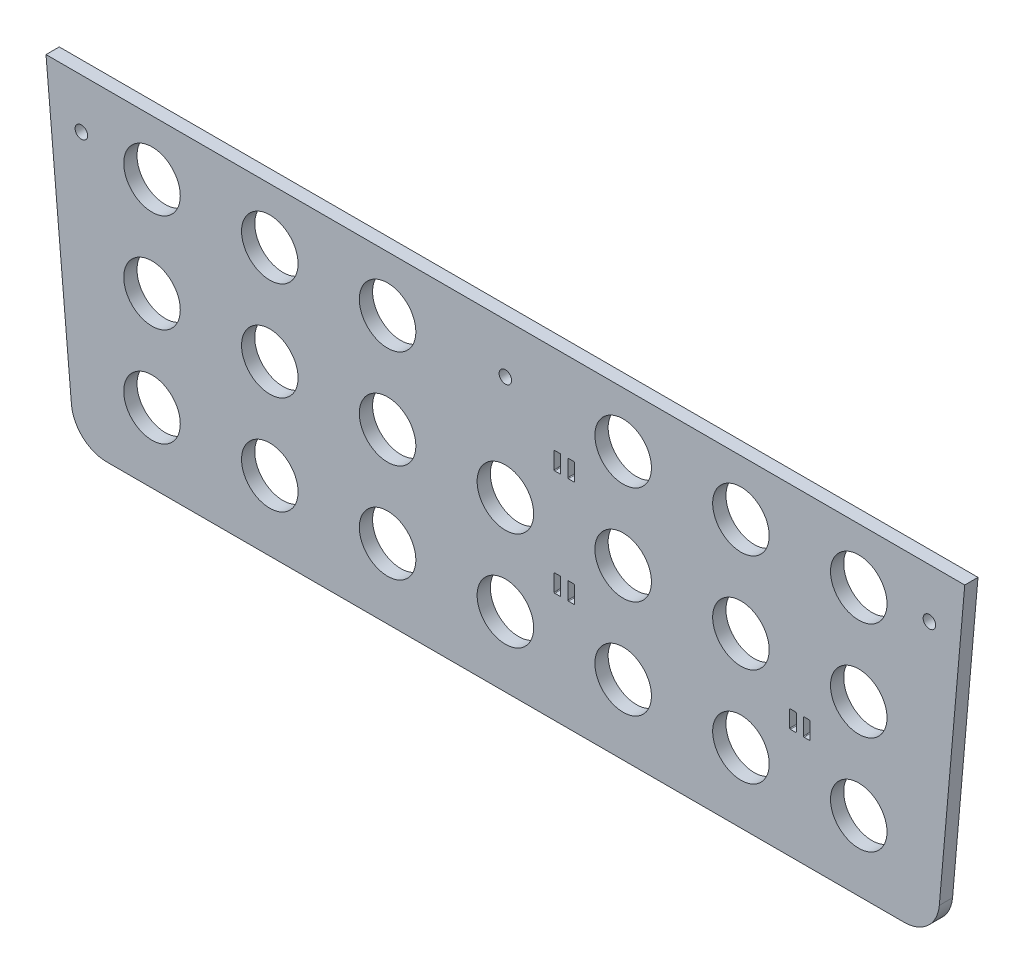
SolidWorks part; units mm, degrees
ref_plane "Front Plane" through (0, 0, 0) normal (0, 0, 1) x (1, 0, 0)
ref_plane "Top Plane" through (0, 0, 0) normal (0, 1, 0) x (1, 0, 0)
ref_plane "Right Plane" through (0, 0, 0) normal (1, 0, 0) x (0, 0, -1)
sketch "Sketch1" plane through (0, 0, 0) normal (0, 0, 1) x (1, 0, 0)
  line L0 (-165.1, 0) -> (165.1, 0)
  line L1 (-143.3047, -115.8875) -> (143.3047, -115.8875)
  line L2 (-165.1, 0) -> (-155.9562, -104.2967)
  line L3 (155.9562, -104.2967) -> (165.1, 0)
  line L4 (0, 0) -> (0, -115.8875) construction
  arc A0 (143.3047, -115.8875) -> (155.9562, -104.2967) centre (143.3047, -103.1875) ccw
  arc A1 (-143.3047, -115.8875) -> (-155.9562, -104.2967) centre (-143.3047, -103.1875) cw
  point P4 (0, 0)
  point P7 (0, -115.8875)
  point P11 (154.94, -115.8875)
  point P14 (-154.94, -115.8875)
  dimension "D4" = 12.7
  dimension "D1" = 115.8875
  dimension "D2" = 330.2
  dimension "D3" = 309.88
extrude "Boss-Extrude1" add sketch "Sketch1" along normal blind 4.7625
hole_wizard "#8 Clearance Hole1" positions "Sketch3" profile "Sketch4" hole size "#8" standard "ANSI Inch" end condition through all
sketch "Sketch3" plane through (0, 0, 4.7625) normal (0, 0, 1) x (1, 0, 0)
  line L0 (165.1, 0) -> (-165.1, 0) construction
  line L1 (0, 0) -> (0, -115.8875) construction
  line L2 (-143.3047, -115.8875) -> (143.3047, -115.8875) construction
  point P9 (-152.4, -17.78)
  point P23 (152.4, -17.78)
  point P24 (0, -17.78)
  dimension "D1" = 17.78
  dimension "D2" = 12.7
sketch "Sketch4" plane through (-152.4, -17.78, 4.7625) normal (1, 0, 0) x (0, -1, 0)
  line L0 (0, 0) -> (0, 4.7625)
  line L1 (0, 4.7625) -> (2.2479, 4.7625)
  line L2 (2.2479, 4.7625) -> (2.2479, 0)
  line L5 (2.2479, 0) -> (0, 0)
  line L11 (0, -6.35) -> (0, 107.95) construction
  dimension "Thru Hole Dia." = 4.4958
  dimension "Thru Hole Depth" = 4.7625
sketch "Sketch8" plane through (0, 0, 4.7625) normal (0, 0, 1) x (1, 0, 0)
  line L0 (0, 0) -> (0, -115.8875) construction
  line L1 (-143.3047, -115.8875) -> (143.3047, -115.8875) construction
  line L3 (-127, -19.8437) -> (0, -19.8437) construction
  circle A0 centre (-127, -19.8437) radius 10.16
  point P7 (0, -57.9437)
  dimension "D1" = 20.32
  dimension "D2" = 127
  dimension "D3" = 38.1
extrude "Holes" cut sketch "Sketch8" against normal through all
pattern_linear "LPattern6" count 7 spacing 42.3333 along (1, 0, 0) count 3 spacing 35.4965 along (0, -1, 0) skipping (3, 0) of "Holes"
sketch "Sketch7" plane through (0, 0, 4.7625) normal (0, 0, 1) x (1, 0, 0)
  line L0 (0, -55.3402) -> (0, -90.8367) construction
  line L1 (17.5154, -76.2635) -> (19.8967, -76.2635)
  line L2 (17.5154, -76.2635) -> (17.5154, -69.9135)
  line L3 (17.5154, -69.9135) -> (19.8967, -69.9135)
  line L4 (19.8967, -76.2635) -> (19.8967, -69.9135)
  line L5 (42.3333, -55.3402) -> (42.3333, -90.8367) construction
  line L6 (42.3333, -73.0885) -> (0, -73.0885) construction
  line L8 (24.8179, -76.2635) -> (22.4367, -76.2635)
  line L9 (22.4367, -76.2635) -> (22.4367, -69.9135)
  line L10 (24.8179, -76.2635) -> (24.8179, -69.9135)
  line L11 (24.8179, -69.9135) -> (22.4367, -69.9135)
  point P4 (21.1667, -73.0885)
  point P23 (21.1667, -73.0885)
  point P24 (19.8967, -73.0885)
  dimension "D1" = 2.3813
  dimension "D2" = 6.35
  dimension "D3" = 2.3813
  dimension "D4" = 2.54
  dimension "D5" = 1.27
extrude "Cut-Extrude2" cut sketch "Sketch7" against normal through all
fillet "Fillet1" radius 0.254 8 edges at (24.8179, -76.2635, 2.3813) (22.4367, -76.2635, 2.3813) (17.5154, -76.2635, 2.3813) (19.8967, -76.2635, 2.3813) (24.8179, -69.9135, 2.3813) (22.4367, -69.9135, 2.3813) (17.5154, -69.9135, 2.3813) (19.8967, -69.9135, 2.3813)
pattern_linear "LPattern7" count 2 spacing 38.1 along (0, 1, 0) count 2 spacing 84.6667 along (1, 0, 0) skipping (1, 1) of "Cut-Extrude2", "Fillet1"
